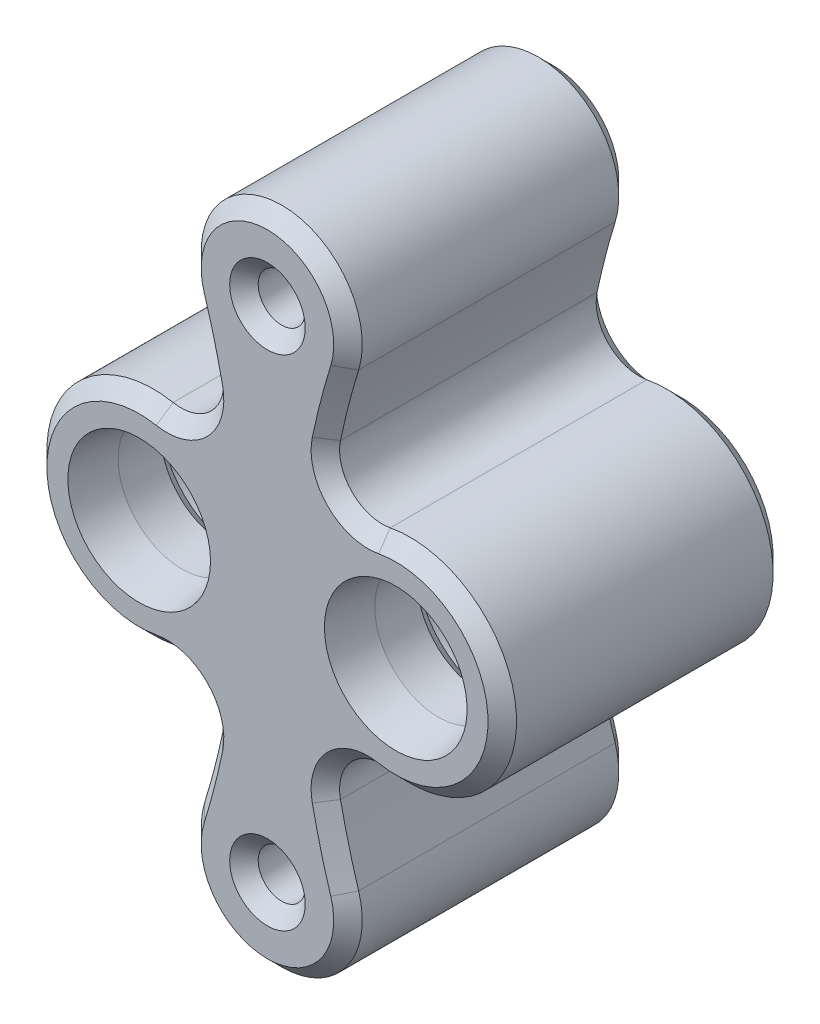
SolidWorks part; units mm, degrees
material "Petg 30% Infill"
ref_plane "Front Plane" through (0, 0, 0) normal (0, 0, 1) x (1, 0, 0)
ref_plane "Top Plane" through (0, 0, 0) normal (0, 1, 0) x (1, 0, 0)
ref_plane "Right Plane" through (0, 0, 0) normal (1, 0, 0) x (0, 0, -1)
sketch "Sketch1" plane through (0, 0, 0) normal (0, 0, 1) x (1, 0, 0)
  line L0 (0, 0) -> (0, -35) construction
  circle A0 centre (0, 0) radius 1.65
  circle A1 centre (0, -35) radius 1.65
  arc A2 (5.3967, -1.6728) -> (-5.3967, -1.6728) centre (0, 0) ccw
  arc A3 (-5.3967, -33.3272) -> (5.3967, -33.3272) centre (0, -35) ccw
  arc A4 (-5.3967, -33.3272) -> (-4.1243, -28.406) centre (-56.458, -17.5) ccw
  arc A5 (5.3967, -33.3272) -> (4.1243, -28.406) centre (56.458, -17.5) cw
  arc A10 (4.1243, -6.594) -> (5.3967, -1.6728) centre (56.458, -17.5) cw
  arc A11 (-4.1243, -6.594) -> (-5.3967, -1.6728) centre (-56.458, -17.5) ccw
  arc A13 (4.1243, -28.406) -> (7.6165, -24.8458) centre (7.0612, -27.794) cw
  arc A14 (-4.1243, -28.406) -> (-7.6165, -24.8458) centre (-7.0612, -27.794) ccw
  arc A15 (-4.1243, -6.594) -> (-7.6165, -10.1542) centre (-7.0612, -7.206) cw
  arc A16 (7.6165, -10.1542) -> (4.1243, -6.594) centre (7.0612, -7.206) cw
  circle A17 centre (9, -17.5) radius 4.475
  circle A18 centre (-9, -17.5) radius 4.475
  arc A23 (7.6165, -24.8458) -> (7.6165, -10.1542) centre (9, -17.5) ccw
  arc A24 (-7.6165, -10.1542) -> (-7.6165, -24.8458) centre (-9, -17.5) ccw
  point P9 (0, -17.5)
  dimension "D1" = 3.3
  dimension "D2" = 4
  dimension "D4" = 6
  dimension "D7" = 3
  dimension "D5" = 3
  dimension "D9" = 8.95
  dimension "D3" = 35
  dimension "D8" = 18
extrude "Boss-Extrude1" add sketch "Sketch1" along normal blind 20
sketch "Sketch4" plane through (0, 0, 20) normal (0, 0, 1) x (1, 0, 0)
chamfer "Chamfer1" distance 1 angle 45 28 edges at (1.65, 0, 0) (1.65, -35, 0) (1.65, 0, 20) (1.65, -35, 20) (4.9195, -25.6933, 0) (16.475, -17.5, 0) (4.702, -30.8818, 0) (4.9195, -9.3067, 0) (0, -40.65, 0) (4.702, -4.1182, 0) (-4.702, -30.8818, 0) (0, 5.65, 0) (-4.9195, -25.6933, 0) (-4.702, -4.1182, 0) (-16.475, -17.5, 0) (-4.9195, -9.3067, 0) (4.9195, -25.6933, 20) (16.475, -17.5, 20) (4.702, -30.8818, 20) (4.9195, -9.3067, 20) (0, -40.65, 20) (4.702, -4.1182, 20) (-4.702, -30.8818, 20) (0, 5.65, 20) (-4.9195, -25.6933, 20) (-4.702, -4.1182, 20) (-16.475, -17.5, 20) (-4.9195, -9.3067, 20)
chamfer "Chamfer2" distance 3 angle 10 4 edges at (13.475, -17.5, 20) (-4.525, -17.5, 20) (-4.525, -17.5, 0) (13.475, -17.5, 0) first distance on face at (13.475, -17.5, 20) first distance on face at (-4.525, -17.5, 20)
ref_plane "Plane1" through (0, 0, 10) normal (0, 0, 1) x (1, 0, 0)
sketch "Sketch5" plane through (0, 0, 10) normal (0, 0, 1) x (1, 0, 0)
  circle A0 centre (-9, -17.5) radius 5.475
  circle A1 centre (9, -17.5) radius 5.475
  circle A2 centre (9, -17.5) radius 4.475 construction
  dimension "D1" = 1
extrude "Cut-Extrude1" cut sketch "Sketch5" against normal blind 3 and the other way blind 3
chamfer "Chamfer3" distance 1 angle 45 4 edges at (-4.525, -17.5, 13) (-4.525, -17.5, 7) (13.475, -17.5, 7) (13.475, -17.5, 13)
